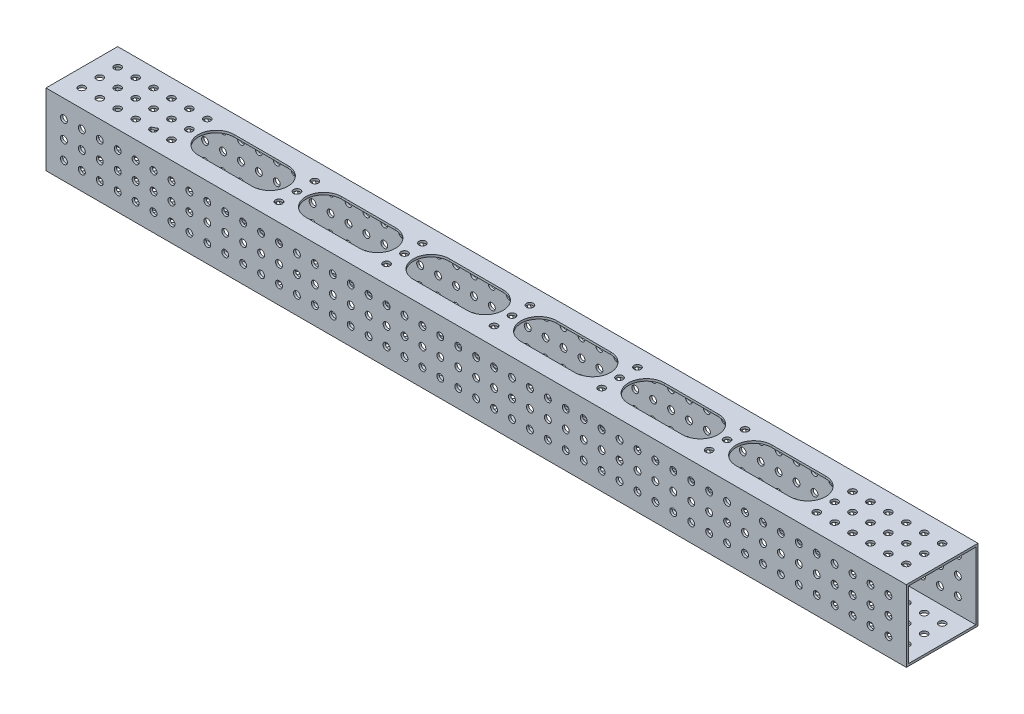
SolidWorks part; units mm, degrees
ref_plane "Front Plane" through (0, 0, 0) normal (0, 0, 1) x (1, 0, 0)
ref_plane "Top Plane" through (0, 0, 0) normal (0, 1, 0) x (1, 0, 0)
ref_plane "Right Plane" through (0, 0, 0) normal (1, 0, 0) x (0, 0, -1)
sketch "Sketch1" plane through (0, 0, 0) normal (1, 0, 0) x (0, 0, -1)
  line L1 (-25.4, -25.4) -> (25.4, -25.4)
  line L2 (-25.4, -25.4) -> (-25.4, 25.4)
  line L3 (-25.4, 25.4) -> (25.4, 25.4)
  line L4 (25.4, -25.4) -> (25.4, 25.4)
  line L5 (-25.4, -25.4) -> (25.4, 25.4) construction
  line L6 (-25.4, 25.4) -> (25.4, -25.4) construction
  line L7 (-23.8125, -23.8125) -> (23.8125, -23.8125)
  line L8 (-23.8125, -23.8125) -> (-23.8125, 23.8125)
  line L9 (-23.8125, 23.8125) -> (23.8125, 23.8125)
  line L10 (23.8125, -23.8125) -> (23.8125, 23.8125)
  line L11 (-23.8125, -23.8125) -> (23.8125, 23.8125) construction
  line L12 (-23.8125, 23.8125) -> (23.8125, -23.8125) construction
  point P0 (0, 0)
  point P7 (0, 0)
  dimension "D1" = 50.8
  dimension "D2" = 50.8
  dimension "D3" = 47.625
extrude "Boss-Extrude1" add sketch "Sketch1" along normal blind 609.6
sketch "Sketch2" plane through (0, 0, 25.4) normal (0, 0, 1) x (1, 0, 0)
  line L0 (-1000, 0) -> (49000, 0) construction
  line L2 (-994.1549, 12.7) -> (49005.8451, 12.7) construction
  line L3 (-984.8446, -12.7) -> (49015.1554, -12.7) construction
  line L4 (609.6, 25.4) -> (0, 25.4) construction
  line L5 (609.6, -25.4) -> (0, -25.4) construction
  line L6 (0, 25.4) -> (0, -25.4) construction
  line L7 (12.7, 12.7) -> (12.7, 0) construction
  line L8 (12.7, 12.7) -> (25.4, 12.7) construction
  circle A24 centre (12.7, 12.7) radius 2.4384
  circle A25 centre (12.7, 0) radius 2.4384
  circle A26 centre (12.7, -12.7) radius 2.4384
  circle A27 centre (25.4, 12.7) radius 2.4384
  circle A28 centre (25.4, 0) radius 2.4384
  circle A29 centre (25.4, -12.7) radius 2.4384
  circle A30 centre (38.1, 12.7) radius 2.4384
  circle A31 centre (38.1, 0) radius 2.4384
  circle A32 centre (38.1, -12.7) radius 2.4384
  circle A33 centre (50.8, 12.7) radius 2.4384
  circle A34 centre (50.8, 0) radius 2.4384
  circle A35 centre (50.8, -12.7) radius 2.4384
  circle A36 centre (63.5, 12.7) radius 2.4384
  circle A37 centre (63.5, 0) radius 2.4384
  circle A38 centre (63.5, -12.7) radius 2.4384
  circle A39 centre (76.2, 12.7) radius 2.4384
  circle A40 centre (76.2, 0) radius 2.4384
  circle A41 centre (76.2, -12.7) radius 2.4384
  circle A42 centre (88.9, 12.7) radius 2.4384
  circle A43 centre (88.9, 0) radius 2.4384
  circle A44 centre (88.9, -12.7) radius 2.4384
  circle A45 centre (101.6, 12.7) radius 2.4384
  circle A46 centre (101.6, 0) radius 2.4384
  circle A47 centre (101.6, -12.7) radius 2.4384
  circle A48 centre (114.3, 12.7) radius 2.4384
  circle A49 centre (114.3, 0) radius 2.4384
  circle A50 centre (114.3, -12.7) radius 2.4384
  circle A51 centre (127, 12.7) radius 2.4384
  circle A52 centre (127, 0) radius 2.4384
  circle A53 centre (127, -12.7) radius 2.4384
  circle A54 centre (139.7, 12.7) radius 2.4384
  circle A55 centre (139.7, 0) radius 2.4384
  circle A56 centre (139.7, -12.7) radius 2.4384
  circle A57 centre (152.4, 12.7) radius 2.4384
  circle A58 centre (152.4, 0) radius 2.4384
  circle A59 centre (152.4, -12.7) radius 2.4384
  circle A60 centre (165.1, 12.7) radius 2.4384
  circle A61 centre (165.1, 0) radius 2.4384
  circle A62 centre (165.1, -12.7) radius 2.4384
  circle A63 centre (177.8, 12.7) radius 2.4384
  circle A64 centre (177.8, 0) radius 2.4384
  circle A65 centre (177.8, -12.7) radius 2.4384
  circle A66 centre (190.5, 12.7) radius 2.4384
  circle A67 centre (190.5, 0) radius 2.4384
  circle A68 centre (190.5, -12.7) radius 2.4384
  circle A69 centre (203.2, 12.7) radius 2.4384
  circle A70 centre (203.2, 0) radius 2.4384
  circle A71 centre (203.2, -12.7) radius 2.4384
  circle A72 centre (215.9, 12.7) radius 2.4384
  circle A73 centre (215.9, 0) radius 2.4384
  circle A74 centre (215.9, -12.7) radius 2.4384
  circle A75 centre (228.6, 12.7) radius 2.4384
  circle A76 centre (228.6, 0) radius 2.4384
  circle A77 centre (228.6, -12.7) radius 2.4384
  circle A78 centre (241.3, 12.7) radius 2.4384
  circle A79 centre (241.3, 0) radius 2.4384
  circle A80 centre (241.3, -12.7) radius 2.4384
  circle A81 centre (254, 12.7) radius 2.4384
  circle A82 centre (254, 0) radius 2.4384
  circle A83 centre (254, -12.7) radius 2.4384
  circle A84 centre (266.7, 12.7) radius 2.4384
  circle A85 centre (266.7, 0) radius 2.4384
  circle A86 centre (266.7, -12.7) radius 2.4384
  circle A87 centre (279.4, 12.7) radius 2.4384
  circle A88 centre (279.4, 0) radius 2.4384
  circle A89 centre (279.4, -12.7) radius 2.4384
  circle A90 centre (292.1, 12.7) radius 2.4384
  circle A91 centre (292.1, 0) radius 2.4384
  circle A92 centre (292.1, -12.7) radius 2.4384
  circle A93 centre (304.8, 12.7) radius 2.4384
  circle A94 centre (304.8, 0) radius 2.4384
  circle A95 centre (304.8, -12.7) radius 2.4384
  circle A96 centre (317.5, 12.7) radius 2.4384
  circle A97 centre (317.5, 0) radius 2.4384
  circle A98 centre (317.5, -12.7) radius 2.4384
  circle A99 centre (330.2, 12.7) radius 2.4384
  circle A100 centre (330.2, 0) radius 2.4384
  circle A101 centre (330.2, -12.7) radius 2.4384
  circle A102 centre (342.9, 12.7) radius 2.4384
  circle A103 centre (342.9, 0) radius 2.4384
  circle A104 centre (342.9, -12.7) radius 2.4384
  circle A105 centre (355.6, 12.7) radius 2.4384
  circle A106 centre (355.6, 0) radius 2.4384
  circle A107 centre (355.6, -12.7) radius 2.4384
  circle A108 centre (368.3, 12.7) radius 2.4384
  circle A109 centre (368.3, 0) radius 2.4384
  circle A110 centre (368.3, -12.7) radius 2.4384
  circle A111 centre (381, 12.7) radius 2.4384
  circle A112 centre (381, 0) radius 2.4384
  circle A113 centre (381, -12.7) radius 2.4384
  circle A114 centre (393.7, 12.7) radius 2.4384
  circle A115 centre (393.7, 0) radius 2.4384
  circle A116 centre (393.7, -12.7) radius 2.4384
  circle A117 centre (406.4, 12.7) radius 2.4384
  circle A118 centre (406.4, 0) radius 2.4384
  circle A119 centre (406.4, -12.7) radius 2.4384
  circle A120 centre (419.1, 12.7) radius 2.4384
  circle A121 centre (419.1, 0) radius 2.4384
  circle A122 centre (419.1, -12.7) radius 2.4384
  circle A123 centre (431.8, 12.7) radius 2.4384
  circle A124 centre (431.8, 0) radius 2.4384
  circle A125 centre (431.8, -12.7) radius 2.4384
  circle A126 centre (444.5, 12.7) radius 2.4384
  circle A127 centre (444.5, 0) radius 2.4384
  circle A128 centre (444.5, -12.7) radius 2.4384
  circle A129 centre (457.2, 12.7) radius 2.4384
  circle A130 centre (457.2, 0) radius 2.4384
  circle A131 centre (457.2, -12.7) radius 2.4384
  circle A132 centre (469.9, 12.7) radius 2.4384
  circle A133 centre (469.9, 0) radius 2.4384
  circle A134 centre (469.9, -12.7) radius 2.4384
  circle A135 centre (482.6, 12.7) radius 2.4384
  circle A136 centre (482.6, 0) radius 2.4384
  circle A137 centre (482.6, -12.7) radius 2.4384
  circle A138 centre (495.3, 12.7) radius 2.4384
  circle A139 centre (495.3, 0) radius 2.4384
  circle A140 centre (495.3, -12.7) radius 2.4384
  circle A141 centre (508, 12.7) radius 2.4384
  circle A142 centre (508, 0) radius 2.4384
  circle A143 centre (508, -12.7) radius 2.4384
  circle A144 centre (520.7, 12.7) radius 2.4384
  circle A145 centre (520.7, 0) radius 2.4384
  circle A146 centre (520.7, -12.7) radius 2.4384
  circle A147 centre (533.4, 12.7) radius 2.4384
  circle A148 centre (533.4, 0) radius 2.4384
  circle A149 centre (533.4, -12.7) radius 2.4384
  circle A150 centre (546.1, 12.7) radius 2.4384
  circle A151 centre (546.1, 0) radius 2.4384
  circle A152 centre (546.1, -12.7) radius 2.4384
  circle A153 centre (558.8, 12.7) radius 2.4384
  circle A154 centre (558.8, 0) radius 2.4384
  circle A155 centre (558.8, -12.7) radius 2.4384
  circle A156 centre (571.5, 12.7) radius 2.4384
  circle A157 centre (571.5, 0) radius 2.4384
  circle A158 centre (571.5, -12.7) radius 2.4384
  circle A159 centre (584.2, 12.7) radius 2.4384
  circle A160 centre (584.2, 0) radius 2.4384
  circle A161 centre (584.2, -12.7) radius 2.4384
  circle A162 centre (596.9, 12.7) radius 2.4384
  circle A163 centre (596.9, 0) radius 2.4384
  circle A164 centre (596.9, -12.7) radius 2.4384
  dimension "D1" = 12.7
  dimension "D3" = 4.8768
  dimension "D2" = 12.7
  dimension "D4" = 12.7
  dimension "D6" = 12.7
  dimension "D8" = 12.7
  dimension "D5" = 3
  dimension "D7" = 47
extrude "Cut-Extrude2" cut sketch "Sketch2" against normal blind 609.6
sketch "Sketch3" plane through (0, -25.4, 0) normal (0, -1, 0) x (1, 0, 0)
  line L0 (0, 0) -> (6.35, 0)
  line L1 (76.2, 12.7) -> (63.5, 12.7) construction
  line L2 (0, 25.4) -> (0, -25.4) construction
  line L3 (19.05, 12.7) -> (57.15, 12.7)
  line L4 (19.05, -12.7) -> (57.15, -12.7)
  line L5 (609.6, 25.4) -> (0, 25.4) construction
  line L6 (95.25, 12.7) -> (133.35, 12.7)
  line L7 (95.25, -12.7) -> (133.35, -12.7)
  line L8 (171.45, 12.7) -> (209.55, 12.7)
  line L9 (171.45, -12.7) -> (209.55, -12.7)
  line L10 (247.65, 12.7) -> (285.75, 12.7)
  line L11 (247.65, -12.7) -> (285.75, -12.7)
  line L12 (323.85, 12.7) -> (361.95, 12.7)
  line L13 (323.85, -12.7) -> (361.95, -12.7)
  line L14 (400.05, 12.7) -> (438.15, 12.7)
  line L15 (400.05, -12.7) -> (438.15, -12.7)
  line L16 (476.25, 12.7) -> (514.35, 12.7)
  line L17 (476.25, -12.7) -> (514.35, -12.7)
  line L18 (552.45, 12.7) -> (590.55, 12.7)
  line L19 (552.45, -12.7) -> (590.55, -12.7)
  line L20 (535.8384, 0) -> (539.75, 0)
  line L21 (527.05, 0) -> (530.9616, 0)
  line L22 (383.4384, 0) -> (387.35, 0)
  line L23 (374.65, 0) -> (378.5616, 0)
  line L24 (459.6384, 0) -> (463.55, 0)
  line L25 (146.05, 0) -> (149.9616, 0)
  line L26 (222.25, 0) -> (226.1616, 0)
  line L27 (154.8384, 0) -> (158.75, 0)
  line L28 (307.2384, 0) -> (311.15, 0)
  line L29 (298.45, 0) -> (302.3616, 0)
  line L30 (231.0384, 0) -> (234.95, 0)
  line L31 (69.85, 0) -> (73.7616, 0)
  line L32 (78.6384, 0) -> (82.55, 0)
  line L33 (19.05, 12.7) -> (95.25, 12.7) construction
  arc A0 (19.05, 12.7) -> (19.05, -12.7) centre (19.05, 0) ccw
  arc A1 (57.15, -12.7) -> (57.15, 12.7) centre (57.15, 0) ccw
  circle A2 centre (76.2, 12.7) radius 2.4384
  circle A3 centre (76.2, 0) radius 2.4384
  circle A4 centre (76.2, -12.7) radius 2.4384
  arc A5 (95.25, 12.7) -> (95.25, -12.7) centre (95.25, 0) ccw
  arc A6 (133.35, -12.7) -> (133.35, 12.7) centre (133.35, 0) ccw
  circle A7 centre (152.4, 12.7) radius 2.4384
  circle A8 centre (152.4, 0) radius 2.4384
  circle A9 centre (152.4, -12.7) radius 2.4384
  arc A10 (171.45, 12.7) -> (171.45, -12.7) centre (171.45, 0) ccw
  arc A11 (209.55, -12.7) -> (209.55, 12.7) centre (209.55, 0) ccw
  circle A12 centre (228.6, 12.7) radius 2.4384
  circle A13 centre (228.6, 0) radius 2.4384
  circle A14 centre (228.6, -12.7) radius 2.4384
  arc A15 (247.65, 12.7) -> (247.65, -12.7) centre (247.65, 0) ccw
  arc A16 (285.75, -12.7) -> (285.75, 12.7) centre (285.75, 0) ccw
  circle A17 centre (304.8, 12.7) radius 2.4384
  circle A18 centre (304.8, 0) radius 2.4384
  circle A19 centre (304.8, -12.7) radius 2.4384
  arc A20 (323.85, 12.7) -> (323.85, -12.7) centre (323.85, 0) ccw
  arc A21 (361.95, -12.7) -> (361.95, 12.7) centre (361.95, 0) ccw
  circle A22 centre (381, 12.7) radius 2.4384
  circle A23 centre (381, 0) radius 2.4384
  circle A24 centre (381, -12.7) radius 2.4384
  arc A25 (400.05, 12.7) -> (400.05, -12.7) centre (400.05, 0) ccw
  arc A26 (438.15, -12.7) -> (438.15, 12.7) centre (438.15, 0) ccw
  circle A27 centre (457.2, 12.7) radius 2.4384
  circle A28 centre (457.2, 0) radius 2.4384
  circle A29 centre (457.2, -12.7) radius 2.4384
  arc A30 (476.25, 12.7) -> (476.25, -12.7) centre (476.25, 0) ccw
  arc A31 (514.35, -12.7) -> (514.35, 12.7) centre (514.35, 0) ccw
  circle A32 centre (533.4, 12.7) radius 2.4384
  circle A33 centre (533.4, 0) radius 2.4384
  circle A34 centre (533.4, -12.7) radius 2.4384
  arc A35 (552.45, 12.7) -> (552.45, -12.7) centre (552.45, 0) ccw
  arc A36 (590.55, -12.7) -> (590.55, 12.7) centre (590.55, 0) ccw
  circle A40 centre (609.6, 12.7) radius 2.4384 [skipped]
  circle A41 centre (609.6, 0) radius 2.4384 [skipped]
  circle A42 centre (609.6, -12.7) radius 2.4384 [skipped]
  circle A43 centre (546.1, 12.7) radius 2.4384
  circle A44 centre (546.1, 0) radius 2.4384
  circle A45 centre (546.1, -12.7) radius 2.4384
  circle A46 centre (558.8, 12.7) radius 2.4384
  circle A47 centre (558.8, 0) radius 2.4384
  circle A48 centre (558.8, -12.7) radius 2.4384
  circle A49 centre (571.5, 12.7) radius 2.4384
  circle A50 centre (571.5, 0) radius 2.4384
  circle A51 centre (571.5, -12.7) radius 2.4384
  circle A52 centre (584.2, 12.7) radius 2.4384
  circle A53 centre (584.2, 0) radius 2.4384
  circle A54 centre (584.2, -12.7) radius 2.4384
  circle A55 centre (596.9, 12.7) radius 2.4384
  circle A56 centre (596.9, 0) radius 2.4384
  circle A57 centre (596.9, -12.7) radius 2.4384
  circle A58 centre (63.5, 12.7) radius 2.4384
  circle A59 centre (63.5, -12.7) radius 2.4384
  circle A60 centre (63.5, 0) radius 2.4384
  circle A61 centre (50.8, 12.7) radius 2.4384
  circle A62 centre (50.8, -12.7) radius 2.4384
  circle A63 centre (50.8, 0) radius 2.4384
  circle A64 centre (38.1, 12.7) radius 2.4384
  circle A65 centre (38.1, -12.7) radius 2.4384
  circle A66 centre (38.1, 0) radius 2.4384
  circle A67 centre (25.4, 12.7) radius 2.4384
  circle A68 centre (25.4, -12.7) radius 2.4384
  circle A69 centre (25.4, 0) radius 2.4384
  circle A70 centre (12.7, 12.7) radius 2.4384
  circle A71 centre (12.7, -12.7) radius 2.4384
  circle A72 centre (12.7, 0) radius 2.4384
  point P11 (0, 0)
  dimension "D1" = 25.4
  dimension "D2" = 19.05
  dimension "D3" = 25.4
  dimension "D4" = 38.1
  dimension "D5" = 4.8768
  dimension ".2" = 4.8768
  dimension "D6" = 4.8768
  dimension "D8" = 12.7
  dimension "D9" = 12.7
  dimension "D10" = 76.2
  dimension "D11" = 76.2
  dimension "D12" = 76.2
  dimension "D7" = 12.7
  dimension "D15" = 76.2
  dimension "D16" = 6
  dimension "D17" = 12.7
  dimension "D13" = 8
  dimension "D14" = 6
extrude "Cut-Extrude3" cut sketch "Sketch3" against normal blind 76.2 contours L7 A6 L6 A5 | L9 A11 L8 A10 | L11 A16 L10 A15 | L13 A21 L12 A20 | A4 | A8 | A9 | A7 | A18 | A23 | L15 A26 L14 A25 | A28 | L17 A31 L16 A30 | A63 | A66 | A69 | A1 A58 | A2 | A3 | A12 | A13 | A14 | A17 | A19 | A22 | A24 | A27 | A29 | A33 | A32 | A34 | A62 | A61 | A64 | A65 | A68 | A67 | A70 | A72 | A71 | A60 | A59 | A45 | A48 | A51 | A44 | A43 | A46 | A49 | A52 | A53 | A50 | A47 | A54 | A57 | A56 | A55 region at (419.1, -25.4, 0) region at (381, -25.4, 0) region at (342.9, -25.4, 0) region at (304.8, -25.4, 0) region at (266.7, -25.4, 0) region at (190.5, -25.4, 0) region at (152.4, -25.4, 0) region at (114.3, -25.4, 0) region at (63.6226, -25.4, 12.9453) region at (457.2, -25.4, 0) region at (495.3, -25.4, 0) region at (76.2, -25.4, -12.7) region at (152.4, -25.4, 12.7) region at (152.4, -25.4, -12.7) region at (50.8, -25.4, 0) region at (38.1, -25.4, 0) region at (25.4, -25.4, 0)
